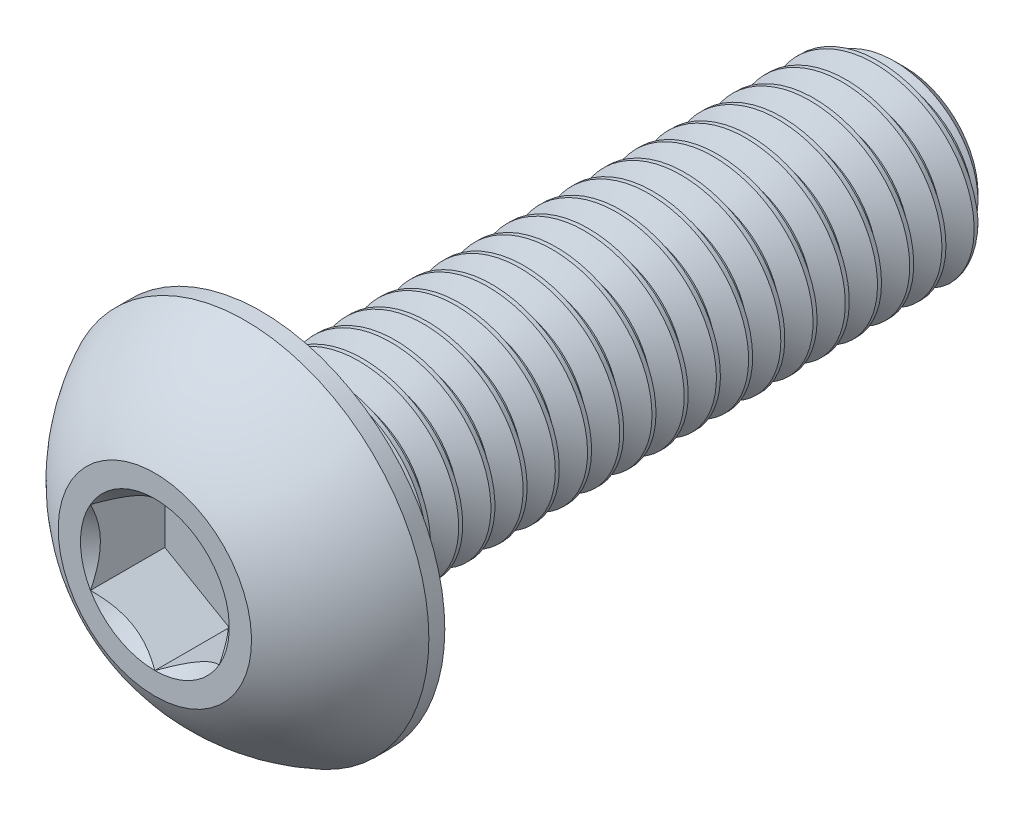
SolidWorks part; units mm, degrees
ref_plane "Front" through (0, 0, 0) normal (0, 0, 1) x (1, 0, 0)
ref_plane "Top" through (0, 0, 0) normal (0, 1, 0) x (1, 0, 0)
ref_plane "Right" through (0, 0, 0) normal (1, 0, 0) x (0, 0, -1)
sketch "Sketch1" plane through (0, 0, 0) normal (1, 0, 0) x (0, 0, -1)
  line L2 (1.65, 1.5) -> (11.65, 1.5)
  line L3 (11.65, 1.5) -> (11.65, 0)
  line L4 (11.65, 0) -> (1.65, 0)
  line L6 (1.4025, 2.85) -> (1.65, 2.85) construction
  line L7 (11.65, 1.5) -> (11.65, -1.5) construction
  line L8 (0, 0) -> (1.65, 0) construction
  line L9 (1.65, 2.85) -> (1.65, -2.85) construction
  line L11 (1.65, 1.5) -> (1.65, 0)
  line L13 (0, 1) -> (0, -1) construction
  line L14 (0, 1) -> (0, 1.5) construction
  arc A3 (0, 1.5) -> (1.4025, 2.85) centre (2.7948, 0) cw construction
  dimension "D1" = 0.2475
  dimension "Head Ht" = 1.65
  dimension "Head Dia" = 5.7
  dimension "Dia" = 3
  dimension "Lg" = 10
  dimension "Hex" = 2
revolve "Revolve1" add sketch "Sketch1" angle 360 about L4
sketch "Sketch3" plane through (0, 0, -11.65) normal (0, 0, -1) x (-1, 0, 0)
  circle A0 centre (0, 0) radius 1.5
curve "Helix/Spiral1" pitch 0.5 height 10.5 radius 1.5 centre (0, 0, -11.65) axis (0, 0, 1) start towards (0, 1, 0)
sketch "Sketch2" plane through (0, 0, 0) normal (1, 0, 0) x (0, 0, -1)
  line L0 (11.65, 1.5) -> (12.0875, 1.5)
  line L1 (12.0875, 1.5) -> (11.9, 1.1752)
  line L2 (11.9, 1.1752) -> (11.8375, 1.1752)
  line L3 (11.8375, 1.1752) -> (11.65, 1.5)
  line L4 (11.7438, 1.3376) -> (11.9938, 1.3376) construction
  dimension "D1" = 60
  dimension "D2" = 0.0625
  dimension "D3" = 0.25
chamfer "Chamfer1" distance 0.375 angle 45 1 edges at (0, 1.5, -11.65)
sweep "Cut-Sweep1" cut profiles "Sketch2" path "Helix/Spiral1"
sketch "Sketch7" plane through (0, 0, 0) normal (1, 0, 0) x (0, 0, -1)
  line L6 (1.4025, 2.85) -> (1.65, 2.85) construction
  line L8 (0, 0) -> (1.65, 0) construction
  line L11 (1.65, 2.85) -> (1.65, -2.85) construction
  line L12 (1.4025, 2.85) -> (1.65, 2.85)
  line L13 (0, 0) -> (1.65, 0)
  line L14 (0, 1) -> (0, -1) construction
  line L15 (1.65, 2.85) -> (1.65, 0)
  line L16 (0, 1.5) -> (0, 0)
  arc A2 (1.4025, 2.85) -> (0, 1.5) centre (2.7948, 0) ccw construction
  arc A3 (1.4025, 2.85) -> (0, 1.5) centre (2.7948, 0) ccw
revolve "Revolve2" add sketch "Sketch7" angle 360 about L13
sketch "Sketch5" plane through (0, 0, 0) normal (0, 0, 1) x (1, 0, 0)
  line L1 (1, -0.5774) -> (1, 0.5774)
  line L2 (1, 0.5774) -> (0, 1.1547)
  line L3 (0, 1.1547) -> (-1, 0.5774)
  line L4 (-1, 0.5774) -> (-1, -0.5774)
  line L5 (-1, -0.5774) -> (0, -1.1547)
  line L6 (0, -1.1547) -> (1, -0.5774)
  circle A0 centre (0, 0) radius 1 construction
extrude "Cut-Extrude2" cut sketch "Sketch5" against normal blind 1.155
sketch "Sketch6" plane through (0, 0, 0) normal (0, 0, 1) x (1, 0, 0)
  circle A0 centre (0, 0) radius 1.1547
extrude "Cut-Extrude3" cut sketch "Sketch6" against normal blind 1.155 draft 45
sketch "Sketch9" [suppressed] plane through (0, 0, -4.2164) normal (0, 0, 1) x (1, 0, 0)
  circle A2 centre (0, 0) radius 3.9687
extrude "Boss-Extrude2" [suppressed] add sketch "Sketch9" against normal offset from surface (9.525 mm away) 28.575 up to face at (0, 1.125, -11.65)
sketch "Sketch10" plane through (0, 0, 0) normal (1, 0, 0) x (0, 0, -1)
  line L0 (11.65, 1.5) -> (11.65, -1.5) construction
  point P0 (10.9, -1.5)
  dimension "D1" = 0.75
equation "\"D3@Helix/Spiral1\" = \"Lg@Sketch1\" + \"D4@Helix/Spiral1\""
equation "\"D2@Sketch2\" = \"D4@Helix/Spiral1\" * .125"
equation "\"D3@Sketch2\" = \"D4@Helix/Spiral1\" * .5"
equation "\"D1@Chamfer1\" = \"D4@Helix/Spiral1\" * .75"
equation "\"D1@Cut-Extrude2\" = \"Head Ht@Sketch1\" * .7"
equation "\"D1@Sketch1\" = \"Head Ht@Sketch1\" * .15"
equation "\"D1@Sketch10\" = \"D4@Helix/Spiral1\" * 1.5"
equation "\"D1@Cut-Extrude3\" = \"D1@Cut-Extrude2\""
